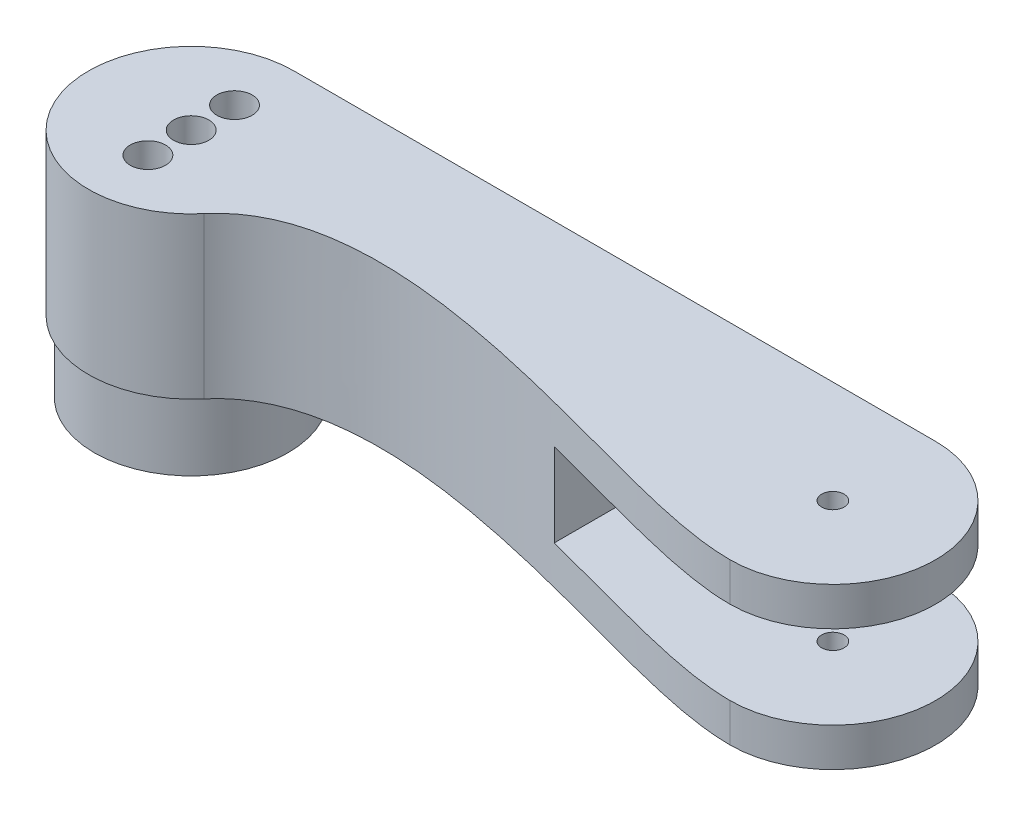
SolidWorks part; units mm, degrees
ref_plane "Front Plane" through (0, 0, 0) normal (0, 0, 1) x (1, 0, 0)
ref_plane "Top Plane" through (0, 0, 0) normal (0, 1, 0) x (1, 0, 0)
ref_plane "Right Plane" through (0, 0, 0) normal (1, 0, 0) x (0, 0, -1)
sketch "Sketch1" plane through (0, 0, 0) normal (0, 1, 0) x (1, 0, 0)
  line L0 (-50, 0) -> (50, 0) construction
  line L1 (-50, 16) -> (50, 16)
  line L2 (-50, -16) -> (50, -16)
  arc A0 (-50, 16) -> (-50, -16) centre (-50, 0) ccw
  arc A1 (50, -16) -> (50, 16) centre (50, 0) ccw
  point P3 (0, 0)
  dimension "D1" = 16
  dimension "D2" = 100
extrude "Boss-Extrude1" add sketch "Sketch1" along normal blind 6
sketch "Sketch3" plane through (0, 0, 0) normal (0, -1, 0) x (1, 0, 0)
  circle A0 centre (50, 0) radius 1.75
  dimension "D1" = 3.5
extrude "Cut-Extrude2" cut sketch "Sketch3" against normal through all
sketch "Sketch4" plane through (0, 6, 0) normal (0, 1, 0) x (1, 0, 0)
  line L0 (-50, 16) -> (15, 16)
  line L1 (-50, 16) -> (50, 16) construction
  line L2 (15, 16) -> (15, -16)
  line L3 (-50, -16) -> (50, -16) construction
  line L4 (15, -16) -> (-50, -16)
  arc A0 (-50, 16) -> (-50, -16) centre (-50, 0) ccw
  arc A1 (-50, 16) -> (-50, -16) centre (-50, 0) ccw construction
  dimension "D1" = 65
extrude "Boss-Extrude2" add sketch "Sketch4" along normal blind 13
sketch "Sketch5" plane through (0, 19, 0) normal (0, 1, 0) x (1, 0, 0)
  line L0 (-50, 0) -> (50, 0) construction
  line L1 (-50, 16) -> (50, 16)
  line L2 (-50, -16) -> (50, -16)
  arc A0 (-50, 16) -> (-50, -16) centre (-50, 0) ccw
  arc A1 (50, -16) -> (50, 16) centre (50, 0) ccw
  point P4 (0, 0)
  dimension "D1" = 16
extrude "Boss-Extrude3" add sketch "Sketch5" along normal blind 6
sketch "Sketch6" plane through (0, 25, 0) normal (0, 1, 0) x (1, 0, 0)
  circle A0 centre (50, 0) radius 1.75
  dimension "D1" = 3.5
extrude "Cut-Extrude3" cut sketch "Sketch6" against normal up to next
sketch "Sketch7" plane through (0, 25, 0) normal (0, 1, 0) x (1, 0, 0)
  line L0 (0, -10.45) -> (0, 10.45) construction
  line L1 (-50, -16) -> (50, -16)
  circle A0 centre (-50, 0) radius 16
  circle A1 centre (50, 0) radius 16
  spline S0 degree 3 poles (-37.7313, -10.2703) (-30.3326, -1.4318) (6.0504, -3.3646) (38.5122, -16) (50, -16) knots 0 0 0 0 0.426661 1 1 1 1
  line M5 (-50, -16) -> (50, -16)
extrude "Cut-Extrude4" cut sketch "Sketch7" against normal up to next contours S0 A0 M5 region at (-6.9153, 25, 11.0131)
sketch "Sketch8" plane through (0, 0, 0) normal (0, -1, 0) x (1, 0, 0)
  circle A1 centre (-50, 0) radius 15.1
  dimension "D1" = 30.2
extrude "Boss-Extrude4" add sketch "Sketch8" along normal blind 11
sketch "Sketch9" plane through (0, -11, 0) normal (0, -1, 0) x (1, 0, 0)
  circle A0 centre (-50, 0) radius 6.75 construction
  circle A1 centre (-50, 6.75) radius 1.75
  circle A2 centre (-50, -6.75) radius 1.75
  arc A3 (-50, 16) -> (-50, -16) centre (-50, 0) ccw construction
  point P6 (-50, 0)
  dimension "D1" = 13.5
  dimension "D2" = 3.5
extrude "Cut-Extrude5" cut sketch "Sketch9" against normal blind 10
sketch "Sketch11" plane through (0, -11, 0) normal (0, -1, 0) x (1, 0, 0)
  circle A0 centre (-50, 0) radius 2.75
  dimension "D1" = 5.5
extrude "Cut-Extrude6" cut sketch "Sketch11" against normal up to next and the other way through all
sketch "Sketch12" plane through (0, -1, 0) normal (0, -1, 0) x (1, 0, 0)
  circle A0 centre (-50, 0) radius 6.75 construction
  circle A1 centre (-50, 6.75) radius 2.75
  circle A2 centre (-50, -6.75) radius 2.75
  circle A3 centre (-50, 6.75) radius 1.75 construction
  dimension "D1" = 5.5
  dimension "D3" = 13.5
  dimension "D2" = 2
extrude "Cut-Extrude7" cut sketch "Sketch12" against normal up to next
equation "\"Length\"= 100mm"
equation "\"Radius\"= 14.25mm"
equation "\"Thick\"= 12mm"
equation "\"D1@Sketch1\"=16"
equation "\"D2@Sketch1\" = \"Length\""
equation "\"D1@Boss-Extrude1\"= \"Thick\""
equation "\"D1@Sketch4\"=\"Length\"*0.65"
equation "\"D1@Sketch5\"=16"
equation "\"D1@Boss-Extrude4\"=\"Thick\"-1"
